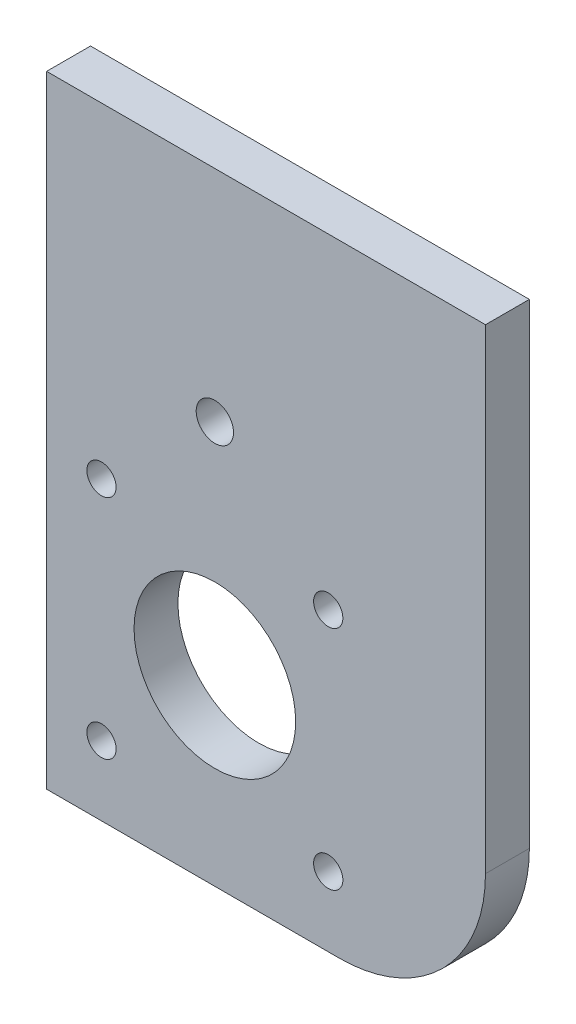
SolidWorks part; units mm, degrees
material "Клен"
ref_plane "Спереди" through (0, 0, 0) normal (0, 0, 1) x (1, 0, 0)
ref_plane "Сверху" through (0, 0, 0) normal (0, 1, 0) x (1, 0, 0)
ref_plane "Справа" through (0, 0, 0) normal (1, 0, 0) x (0, 0, -1)
sketch "Эскиз1" plane through (0, 0, 0) normal (0, 0, 1) x (1, 0, 0)
  line L0 (6, -293.8462) -> (6, -378.8462)
  line L1 (6, -293.8462) -> (6, -593.8462) construction
  line L7 (6, -293.8462) -> (66, -293.8462)
  line L9 (66, -293.8462) -> (66, -287.8462) construction
  line L12 (66, -293.8462) -> (66, -358.8462)
  line L14 (46, -378.8462) -> (6, -378.8462)
  arc A0 (66, -358.8462) -> (46, -378.8462) centre (46, -358.8462) cw
  circle A1 centre (29, -323.8462) radius 2.55
  dimension "D3" = 5.1
  dimension "D2" = 20
  dimension "D1" = 85
extrude "Бобышка-Вытянуть1" add sketch "Эскиз1" against normal blind 6 contours L0 L14 A0 L12 L7
sketch "Эскиз2" plane through (0, 0, 0) normal (0, 0, 1) x (1, 0, 0)
  line L0 (6, -293.8462) -> (6, -378.8462) construction
  line L2 (29, -353.8462) -> (29, -402.3555) construction
  line L3 (29, -353.8462) -> (54.8419, -353.8462) construction
  line L5 (6, -293.8462) -> (66, -293.8462) construction
  circle A0 centre (29, -353.8462) radius 11.05
  circle A1 centre (44.5, -369.3462) radius 2
  circle A2 centre (13.5, -369.3462) radius 2
  circle A3 centre (13.5, -338.3462) radius 2
  circle A4 centre (44.5, -338.3462) radius 2
  circle A5 centre (29, -323.8462) radius 2.55
  dimension "D2" = 22.1
  dimension "D3" = 4
  dimension "D6" = 5.1
  dimension "D1" = 60
  dimension "D4" = 15.5
  dimension "D5" = 15.5
  dimension "D7" = 23
extrude "Вырез-Вытянуть1" cut sketch "Эскиз2" against normal through all
